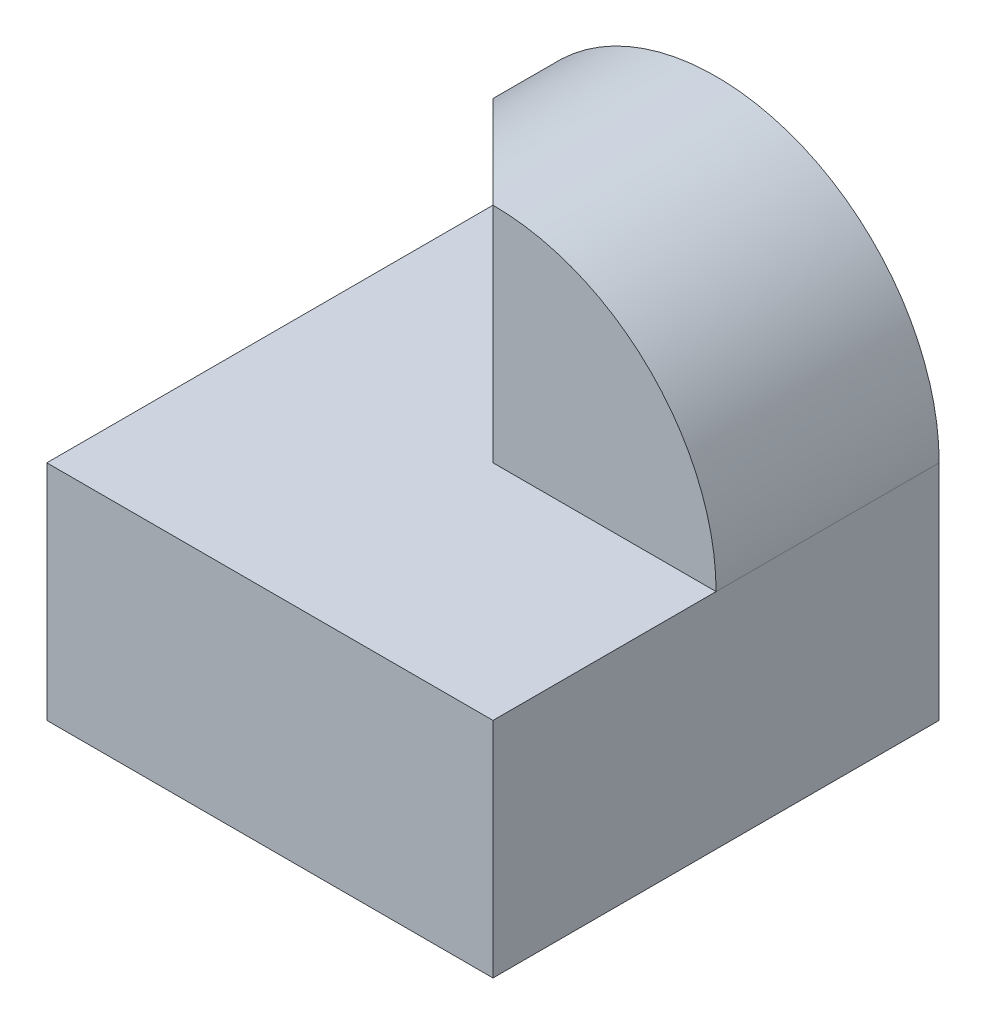
SolidWorks part; units mm, degrees
ref_plane "Front" through (0, 0, 0) normal (0, 0, 1) x (1, 0, 0)
ref_plane "Top" through (0, 0, 0) normal (0, 1, 0) x (1, 0, 0)
ref_plane "Right" through (0, 0, 0) normal (1, 0, 0) x (0, 0, -1)
sketch "Sketch1" plane through (0, 0, 0) normal (0, 1, 0) x (1, 0, 0)
  line L1 (-2, -2) -> (2, -2)
  line L2 (-2, -2) -> (-2, 2)
  line L3 (-2, 2) -> (2, 2)
  line L4 (2, -2) -> (2, 2)
  line L5 (-2, -2) -> (2, 2) construction
  line L6 (-2, 2) -> (2, -2) construction
  point P0 (0, 0)
  dimension "D1" = 4
  dimension "D2" = 4
extrude "Boss-Extrude1" add sketch "Sketch1" along normal blind 4
sketch "Sketch2" plane through (0, 0, 2) normal (0, 0, 1) x (1, 0, 0)
  line L0 (2, 4) -> (2, 0) construction
  line L1 (-2, 4) -> (2, 4)
  line L2 (-2, 4) -> (-2, 2)
  line L3 (-2, 2) -> (2, 2)
  line L4 (2, 4) -> (2, 2)
extrude "Cut-Extrude1" cut sketch "Sketch2" against normal blind 2
sketch "Sketch3" plane through (0, 0, -2) normal (0, 0, -1) x (-1, 0, 0)
  line L0 (2, 2) -> (0, 0)
  line L1 (2, 4) -> (2, 0) construction
  line L2 (-2, 0) -> (2, 0) construction
  line L3 (0, 0) -> (2, 0)
  line L4 (2, 0) -> (2, 2)
extrude "Cut-Extrude2" cut sketch "Sketch3" against normal blind 2
sketch "Sketch4" plane through (0, 0, 0) normal (0, 0, 1) x (1, 0, 0)
  line L0 (-2, 2) -> (-2, 4)
  line L1 (-2, 4) -> (2, 4)
  line L2 (2, 4) -> (2, 2)
  arc A0 (-2, 2) -> (2, 2) centre (0, 2) cw
  line M1 (-2, 4) -> (-2, 2)
  line M3 (2, 2) -> (2, 4)
  line M4 (2, 4) -> (-2, 4)
extrude "Cut-Extrude3" cut sketch "Sketch4" against normal blind 2 contours A0 L1 M1 | A0 M4 M3
sketch "Sketch5" plane through (0, 2, 0) normal (0, 1, 0) x (1, 0, 0)
  line L0 (0, 0) -> (-2, 2)
  line L1 (-2, 0) -> (2, 0) construction
  line L2 (-2, 2) -> (-2, 0)
  line L3 (-2, 0) -> (0, 0)
extrude "Cut-Extrude4" cut sketch "Sketch5" along normal blind 2
